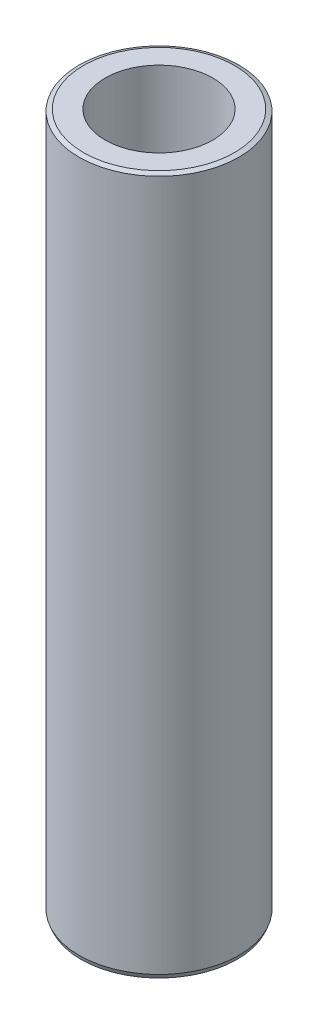
SolidWorks part; units mm, degrees
ref_plane "Front Plane" through (0, 0, 0) normal (0, 0, 1) x (1, 0, 0)
ref_plane "Top Plane" through (0, 0, 0) normal (0, 1, 0) x (1, 0, 0)
ref_plane "Right Plane" through (0, 0, 0) normal (1, 0, 0) x (0, 0, -1)
sketch "Sketch1" plane through (0, 0, 0) normal (0, 1, 0) x (1, 0, 0)
  circle A0 centre (0, 0) radius 20
  dimension "SHAFT_OD" = 40
extrude "Boss-Extrude1" add sketch "Sketch1" along normal blind 174.5735
sketch "Sketch2" plane through (0, 0, 0) normal (0, 1, 0) x (1, 0, 0)
  circle A0 centre (0, 0) radius 13.4767
  dimension "BORE_D" = 26.9534
extrude "Cut-Extrude1" cut sketch "Sketch2" along normal through all
chamfer "Chamfer1" distance 0.451 angle 67.734 2 edges at (0, 174.5735, 20) (0, 0, 20) first distance on face at (0, 174.5735, 20) first distance on face at (0, 0, 13.4767)
